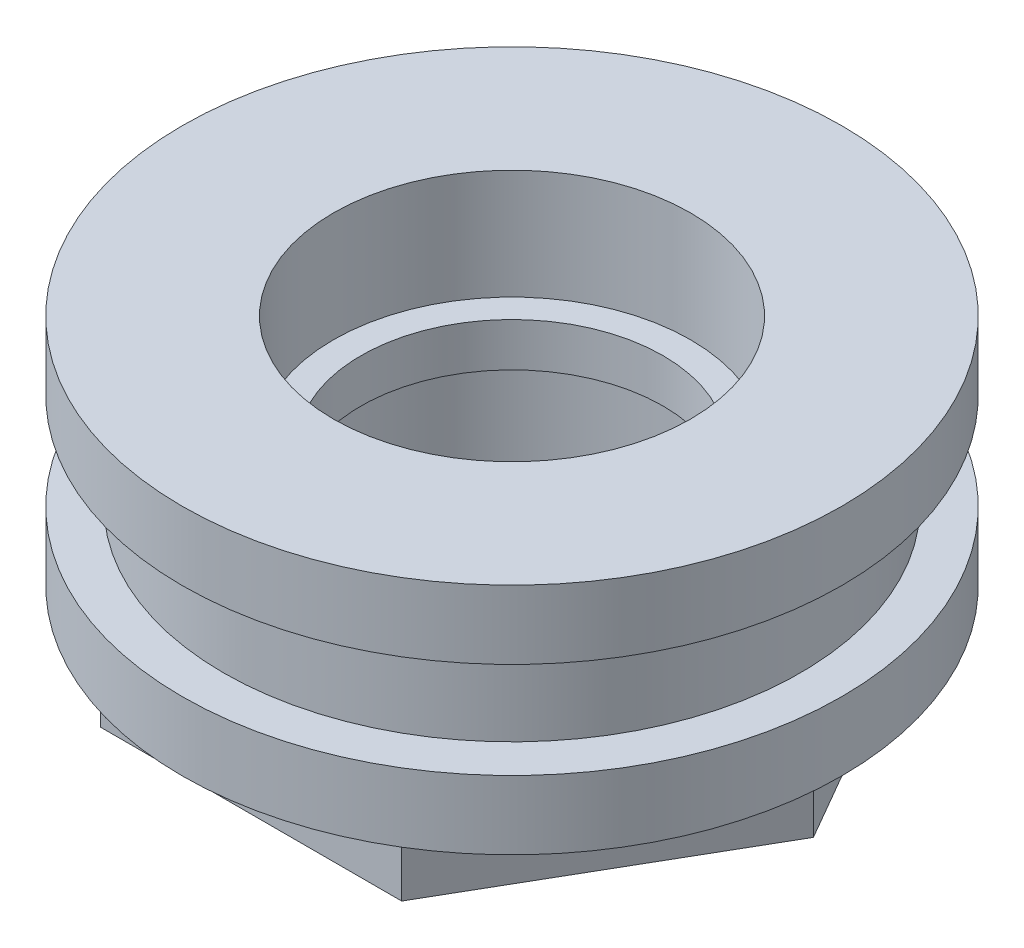
SolidWorks part; units mm, degrees
ref_plane "Front Plane" through (0, 0, 0) normal (0, 0, 1) x (1, 0, 0)
ref_plane "Top Plane" through (0, 0, 0) normal (0, 1, 0) x (1, 0, 0)
ref_plane "Right Plane" through (0, 0, 0) normal (1, 0, 0) x (0, 0, -1)
sketch "Sketch2" plane through (0, 0, 0) normal (0, 0, 1) x (1, 0, 0)
  line L0 (0, 17.2621) -> (0, -17.2621) construction
  line L1 (11, 1.5875) -> (13, 1.5875)
  line L2 (13, 1.5875) -> (13, 9.5875)
  line L3 (13, 9.5875) -> (24, 9.5875)
  line L4 (24, 9.5875) -> (24, 4.5875)
  line L5 (24, 4.5875) -> (21, 4.5875)
  line L6 (21, 4.5875) -> (21, -2.4125)
  line L7 (21, -2.4125) -> (24, -2.4125)
  line L8 (24, -2.4125) -> (24, -7.4125)
  line L9 (24, -7.4125) -> (15, -7.4125)
  line L10 (15, -7.4125) -> (15, -12.3125)
  line L11 (15, -12.3125) -> (13, -12.3125)
  line L12 (13, -12.3125) -> (13, -1.5875)
  line L13 (13, -1.5875) -> (11, -1.5875)
  line L14 (11, -1.5875) -> (11, 1.5875)
  point P3 (11, 0)
  point P4 (0, 0)
  dimension "D1" = 7
  dimension "D2" = 26
  dimension "D3" = 8
  dimension "D4" = 2
  dimension "D5" = 5
  dimension "D6" = 3
  dimension "D7" = 3.175
  dimension "D8" = 5
  dimension "D9" = 42
  dimension "D10" = 2
  dimension "D11" = 4.9
revolve "Revolve1" add sketch "Sketch2" angle 360 about L0
sketch "Sketch8" plane through (0, -7.4125, 0) normal (0, -1, 0) x (1, 0, 0)
  line L1 (21.9393, 0) -> (10.9697, 19)
  line L2 (10.9697, 19) -> (-10.9697, 19)
  line L3 (-10.9697, 19) -> (-21.9393, 0)
  line L4 (-21.9393, 0) -> (-10.9697, -19)
  line L5 (-10.9697, -19) -> (10.9697, -19)
  line L6 (10.9697, -19) -> (21.9393, 0)
  circle A0 centre (0, 0) radius 19 construction
  circle A1 centre (0, 0) radius 15 construction
  dimension "D1" = 4
extrude "Boss-Extrude1" add sketch "Sketch8" along normal up to surface (4.9 mm away) up to face at (0, -12.3125, 15)
sketch "Sketch9" plane through (0, -12.3125, 0) normal (0, -1, 0) x (1, 0, 0)
  line L1 (17.5, 0) -> (8.75, 15.1554) construction
  line L2 (8.75, 15.1554) -> (-8.75, 15.1554) construction
  line L3 (-8.75, 15.1554) -> (-17.5, 0) construction
  line L4 (-17.5, 0) -> (-8.75, -15.1554) construction
  line L5 (-8.75, -15.1554) -> (8.75, -15.1554) construction
  line L6 (8.75, -15.1554) -> (17.5, 0) construction
  circle A0 centre (0, 0) radius 15.1554 construction
  circle A1 centre (0, 0) radius 17.5 construction
  point P12 (-17.5, 0)
  point P13 (-8.75, -15.1554)
  point P14 (-8.75, 15.1554)
  point P15 (8.75, -15.1554)
  point P16 (17.5, 0)
  point P17 (8.75, 15.1554)
  dimension "D1" = 35
hole_wizard "M4x0.7 Tapped Hole3" positions "Sketch9" profile "Sketch10" tap size "M4x0.7" standard "ANSI Metric"
sketch "Sketch10" plane through (8.75, -12.3125, 15.1554) normal (1, 0, 0) x (0, 0, -1)
  line L0 (0, 0) -> (0, 11.0914)
  line L1 (0, 11.0914) -> (1.65, 10.1)
  line L2 (1.65, 10.1) -> (1.65, 0)
  line L5 (1.65, 0) -> (0, 0)
  line L10 (0, 11.0914) -> (-1.65, 10.1) construction
  line L11 (0, -6.35) -> (0, 107.95) construction
  dimension "Tap Drill Dia." = 3.3
  dimension "Tap Drill Depth" = 10.1
  dimension "Drill Angle" = 118
cosmetic thread "Hole Thread11" parameters "D1"=8, "D2"=4
cosmetic thread "Hole Thread12" parameters "D1"=8, "D2"=4
cosmetic thread "Hole Thread13" parameters "D1"=8, "D2"=4
cosmetic thread "Hole Thread14" parameters "D1"=8, "D2"=4
cosmetic thread "Hole Thread15" parameters "D1"=8, "D2"=4
cosmetic thread "Hole Thread16" parameters "D1"=8, "D2"=4
sketch "Sketch11" plane through (0, -7.4125, 0) normal (0, 1, 0) x (1, 0, 0)
  circle A0 centre (0, 0) radius 13
  circle A2 centre (0, 0) radius 13 construction
extrude "Cut-Extrude1" cut sketch "Sketch11" against normal through all
chamfer "Chamfer1" distance 1.5 angle 45 6 edges at (-8.75, -12.3125, -16.8054) (8.75, -12.3125, -16.8054) (17.5, -12.3125, -1.65) (8.75, -12.3125, 13.5054) (-8.75, -12.3125, 13.5054) (-17.5, -12.3125, -1.65)
